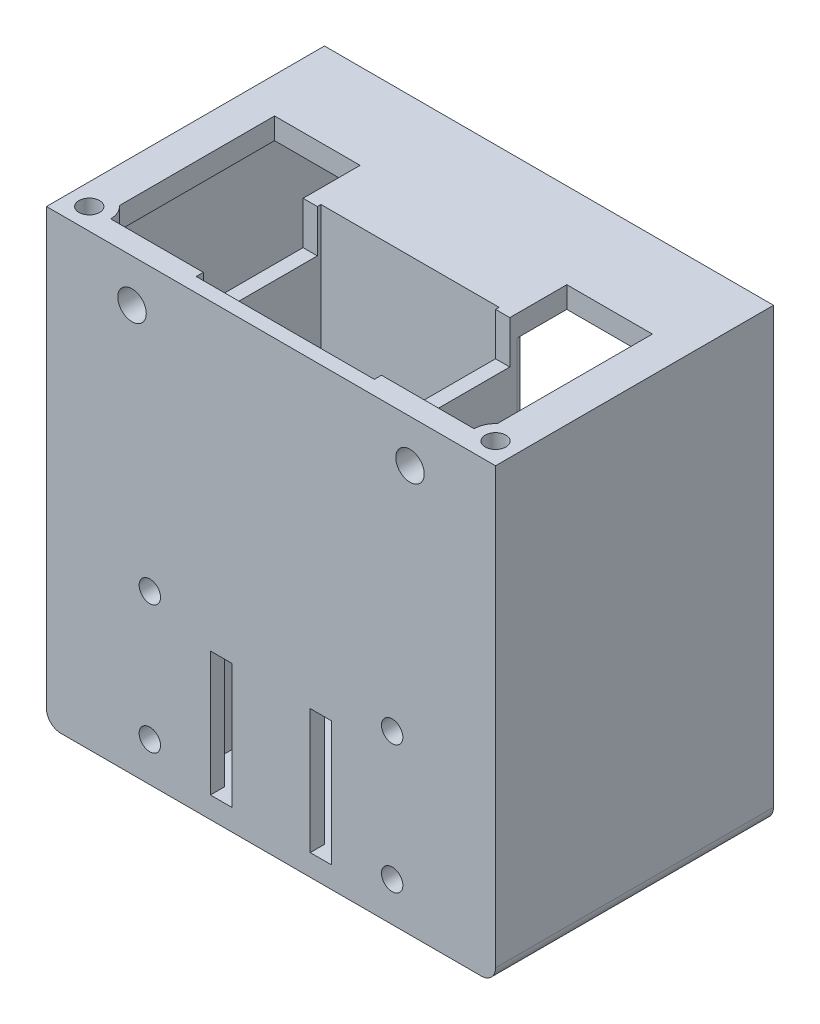
SolidWorks part; units mm, degrees
ref_plane "Alzado" through (0, 0, 0) normal (0, 0, 1) x (1, 0, 0)
ref_plane "Planta" through (0, 0, 0) normal (0, 1, 0) x (1, 0, 0)
ref_plane "Vista lateral" through (0, 0, 0) normal (1, 0, 0) x (0, 0, -1)
sketch "Croquis1" plane through (0, 0, 0) normal (0, 0, 1) x (1, 0, 0)
  line L1 (0, 0) -> (63, 0)
  line L2 (0, 0) -> (0, 63)
  line L3 (0, 63) -> (63, 63)
  line L4 (63, 0) -> (63, 63)
  line L5 (23, 20.5) -> (26, 20.5)
  line L6 (23, 20.5) -> (23, 8.5)
  line L7 (23, 8.5) -> (26, 8.5)
  line L8 (26, 20.5) -> (26, 8.5)
  line L9 (37, 20.5) -> (40, 20.5)
  line L10 (37, 20.5) -> (37, 8.5)
  line L11 (37, 8.5) -> (40, 8.5)
  line L12 (40, 20.5) -> (40, 8.5)
  circle A0 centre (12, 57) radius 2
  circle A1 centre (51, 57) radius 2
  circle A2 centre (14.5, 5.5) radius 1.5
  circle A3 centre (14.5, 23.5) radius 1.5
  circle A4 centre (48.5, 5.5) radius 1.5
  circle A5 centre (48.5, 23.5) radius 1.5
  point P21 (24.5, 8.5)
  dimension "D2" = 4
  dimension "D3" = 4
  dimension "D8" = 3
  dimension "D9" = 3
  dimension "D10" = 3
  dimension "D11" = 3
  dimension "D1" = 63
  dimension "D4" = 12
  dimension "D5" = 12
  dimension "D6" = 6
  dimension "D7" = 6
  dimension "D12" = 14.5
  dimension "D13" = 14.5
  dimension "D14" = 14.5
  dimension "D15" = 14.5
  dimension "D16" = 18
  dimension "D17" = 18
  dimension "D18" = 5.5
  dimension "D19" = 5.5
  dimension "D20" = 12
  dimension "D21" = 3
  dimension "D22" = 8.5
  dimension "D23" = 8.5
  dimension "D24" = 12
  dimension "D25" = 3
  dimension "D26" = 8.5
  dimension "D27" = 8.5
extrude "Saliente-Extruir1" add sketch "Croquis1" along normal blind 3
sketch "Croquis2" plane through (0, 0, 0) normal (0, 0, -1) x (-1, 0, 0)
  line L1 (0, 0) -> (-63, 0)
  line L2 (0, 0) -> (0, 63)
  line L3 (0, 63) -> (-63, 63)
  line L4 (-63, 0) -> (-63, 63)
  line L5 (-3, 3) -> (-60, 3)
  line L6 (-3, 3) -> (-3, 60)
  line L7 (-3, 60) -> (-60, 60)
  line L8 (-60, 3) -> (-60, 60)
  dimension "D1" = 57
  dimension "D2" = 57
  dimension "D3" = 3
  dimension "D4" = 3
extrude "Saliente-Extruir2" add sketch "Croquis2" along normal blind 36
sketch "Croquis4" plane through (0, 63, 0) normal (0, 1, 0) x (1, 0, 0)
  line L0 (63, -3) -> (0, -3) construction
  line L1 (19, 16) -> (44, 16)
  line L2 (19, 16) -> (19, -1)
  line L3 (19, -1) -> (44, -1)
  line L4 (44, 16) -> (44, -1)
  line L5 (0, -3) -> (0, 36) construction
  dimension "D1" = 25
  dimension "D2" = 17
  dimension "D3" = 2
  dimension "D4" = 19
extrude "Cortar-Extruir2" cut sketch "Croquis4" against normal blind 60
sketch "Croquis12" plane through (0, 63, 0) normal (0, 1, 0) x (1, 0, 0)
  line L0 (19, -1) -> (17, -1)
  line L2 (19, -1) -> (19, 16)
  line L3 (19, 16) -> (44, 16)
  line L4 (44, -1) -> (44, 16)
  line L6 (17, -1) -> (17, 18)
  line L7 (17, 18) -> (46, 18)
  line L8 (46, -1) -> (46, 18)
  line L9 (44, -1) -> (46, -1)
  dimension "D1" = 2
  dimension "D2" = 2
  dimension "D3" = 2
extrude "Saliente-Extruir8" add sketch "Croquis12" against normal blind 60
sketch "Croquis8" plane through (0, 0, 0) normal (-1, 0, 0) x (0, 0, 1)
  line L0 (3, 63) -> (3, 0) construction
  line L1 (-3, 20.5) -> (0, 20.5)
  line L2 (-3, 20.5) -> (-3, 8.5)
  line L3 (-3, 8.5) -> (0, 8.5)
  line L4 (0, 20.5) -> (0, 8.5)
  line L5 (3, 0) -> (-36, 0) construction
  dimension "D1" = 12
  dimension "D2" = 3
  dimension "D3" = 3
  dimension "D4" = 8.5
extrude "Cortar-Extruir4" cut sketch "Croquis8" against normal blind 63
sketch "Croquis10" plane through (0, 0, -36) normal (0, 0, -1) x (-1, 0, 0)
  circle A0 centre (-3, 3) radius 3
  circle A1 centre (-60, 3) radius 3
  dimension "D1" = 6
  dimension "D2" = 6
extrude "Saliente-Extruir6" add sketch "Croquis10" against normal blind 20
sketch "Croquis11" plane through (0, 0, -36) normal (0, 0, -1) x (-1, 0, 0)
  circle A3 centre (-60, 3) radius 1.45
  circle A5 centre (-3, 3) radius 1.45
  dimension "D4" = 2.9
  dimension "D5" = 2.9
extrude "Cortar-Extruir6" cut sketch "Croquis11" against normal blind 9
fillet "Redondeo1" radius 2 2 edges at (63, 0, -16.5) (0, 0, -16.5)
sketch "Croquis13" plane through (0, 0, -18) normal (0, 0, -1) x (-1, 0, 0)
  line L0 (-46, 3) -> (-17, 3) construction
  line L1 (-44, 3) -> (-19, 3)
  line L2 (-44, 3) -> (-44, 28)
  line L3 (-44, 28) -> (-19, 28)
  line L4 (-19, 3) -> (-19, 28)
  line L5 (-46, 3) -> (-46, 60) construction
  line L6 (-17, 3) -> (-17, 60) construction
  dimension "D1" = 2
  dimension "D2" = 2
  dimension "D3" = 25
extrude "Cortar-Extruir7" cut sketch "Croquis13" against normal blind 3
sketch "Croquis14" plane through (0, 63, 0) normal (0, 1, 0) x (1, 0, 0)
  line L0 (44, 18) -> (44, -1) construction
  line L1 (46, 20) -> (58, 20)
  line L2 (46, 20) -> (46, 0)
  line L3 (46, 0) -> (58, 0)
  line L4 (58, 20) -> (58, 0)
  line L5 (17, 0) -> (5, 0)
  line L6 (17, 0) -> (17, 20)
  line L7 (17, 20) -> (5, 20)
  line L8 (5, 0) -> (5, 20)
  line L9 (19, -1) -> (19, 18) construction
  line L10 (63, -3) -> (0, -3) construction
  dimension "D1" = 2
  dimension "D2" = 2
  dimension "D3" = 3
  dimension "D4" = 3
  dimension "D5" = 12
  dimension "D6" = 20
  dimension "D7" = 12
  dimension "D8" = 20
extrude "Cortar-Extruir8" cut sketch "Croquis14" against normal blind 5
sketch "Croquis15" plane through (0, 63, 0) normal (0, 1, 0) x (1, 0, 0)
  line L0 (63, -3) -> (0, -3) construction
  line L1 (0, -3) -> (0, 36) construction
  line L3 (63, -3) -> (63, 36) construction
  line L4 (0, 36) -> (63, 36) construction
  circle A0 centre (3, 0) radius 3
  circle A1 centre (60, 0) radius 3
  circle A2 centre (31.5, 31) radius 3
  dimension "D1" = 6
  dimension "D2" = 6
  dimension "D3" = 6
  dimension "D4" = 31.5
  dimension "D5" = 5
extrude "Saliente-Extruir9" add sketch "Croquis15" against normal blind 20
sketch "Croquis16" plane through (0, 60, 0) normal (0, -1, 0) x (1, 0, 0)
  line L0 (17, -18) -> (46, -18) construction
  line L1 (24, -18) -> (39, -18)
  line L2 (24, -18) -> (24, -36)
  line L3 (24, -36) -> (39, -36)
  line L4 (39, -18) -> (39, -36)
  line L5 (3, -36) -> (60, -36) construction
extrude "Saliente-Extruir10" add sketch "Croquis16" along normal blind 8
sketch "Croquis17" plane through (0, 63, 0) normal (0, 1, 0) x (1, 0, 0)
  line L0 (0, 36) -> (63, 36) construction
  line L1 (0, -3) -> (0, 36) construction
  circle A0 centre (3, 0) radius 1.45
  circle A1 centre (60, 0) radius 1.45
  circle A2 centre (31.5, 31) radius 1.45
  dimension "D1" = 2.9
  dimension "D2" = 2.9
  dimension "D3" = 2.9
  dimension "D4" = 5
  dimension "D5" = 31.5
extrude "Cortar-Extruir9" cut sketch "Croquis17" against normal blind 20
sketch "Croquis18" plane through (63, 0, 0) normal (1, 0, 0) x (0, 0, -1)
  line L1 (0, 8.5) -> (3, 8.5)
  line L2 (0, 8.5) -> (0, 20.5)
  line L3 (0, 20.5) -> (3, 20.5)
  line L4 (3, 8.5) -> (3, 20.5)
extrude "Saliente-Extruir11" add sketch "Croquis18" against normal blind 3
sketch "Croquis19" plane through (0, 0, 0) normal (-1, 0, 0) x (0, 0, 1)
  line L1 (-3, 8.5) -> (0, 8.5)
  line L2 (-3, 8.5) -> (-3, 20.5)
  line L3 (-3, 20.5) -> (0, 20.5)
  line L4 (0, 8.5) -> (0, 20.5)
extrude "Saliente-Extruir12" add sketch "Croquis19" against normal blind 3
fillet "Redondeo3" radius 1 10 edges at (31.5, 28, -18) (44, 15.5, -18) (19, 15.5, -18) (46, 31.5, -18) (17, 31.5, -18) (39, 52, -27) (24, 52, -27) (39, 56, -36) (24, 56, -36) (31.5, 52, -36)
sketch "Croquis20" plane through (0, 0, 0) normal (0, -1, 0) x (1, 0, 0)
  line L0 (2, 3) -> (61, 3) construction
  line L1 (0, -36) -> (0, 3) construction
  circle A0 centre (10, -4) radius 3.125
  circle A1 centre (10, -14) radius 2.625
  dimension "D1" = 6.25
  dimension "D3" = 5.25
  dimension "D2" = 7
  dimension "D4" = 10
  dimension "D5" = 10
  dimension "D6" = 10
extrude "Cortar-Extruir10" cut sketch "Croquis20" against normal blind 3
sketch "Croquis21" plane through (0, 0, -36) normal (0, 0, -1) x (-1, 0, 0)
  line L0 (-3, 60) -> (-25, 60) construction
  line L1 (-22.4776, 60) -> (-41.3134, 60)
  line L2 (-22.4776, 60) -> (-22.4776, 40.1042)
  line L3 (-22.4776, 40.1042) -> (-41.3134, 40.1042)
  line L4 (-41.3134, 60) -> (-41.3134, 40.1042)
extrude "Cortar-Extruir11" cut sketch "Croquis21" against normal up to surface (18 mm away) up to face at (31.5, 50.7586, -18)
sketch "Croquis22" plane through (0, 63, 0) normal (0, 1, 0) x (1, 0, 0)
  circle A0 centre (31.5, 31) radius 1.45
extrude "Saliente-Extruir13" add sketch "Croquis22" against normal up to surface (3 mm away)
sketch "Croquis23" plane through (0, 63, 0) normal (0, 1, 0) x (1, 0, 0)
  line L0 (46, 0) -> (46, 17) construction
  line L1 (17, 0) -> (46, 0)
  line L2 (17, 0) -> (17, 16)
  line L3 (17, 16) -> (46, 16)
  line L4 (46, 0) -> (46, 16)
  line L5 (44, 16) -> (19, 16) construction
extrude "Cortar-Extruir12" cut sketch "Croquis23" against normal blind 6
sketch "Croquis24" plane through (0, 0, 1) normal (0, 0, -1) x (-1, 0, 0)
  line L0 (-57, 3) -> (-6, 3) construction
  line L1 (-40, 8.5) -> (-37, 8.5)
  line L2 (-40, 8.5) -> (-40, 3)
  line L3 (-40, 3) -> (-37, 3)
  line L4 (-37, 8.5) -> (-37, 3)
  line L5 (-37, 20.5) -> (-37, 8.5) construction
  line L6 (-19, 3) -> (-44, 3) construction
  line L7 (-26, 8.5) -> (-23, 8.5)
  line L8 (-26, 8.5) -> (-26, 3)
  line L9 (-26, 3) -> (-23, 3)
  line L10 (-23, 8.5) -> (-23, 3)
  line L11 (-23, 20.5) -> (-23, 8.5) construction
extrude "Cortar-Extruir13" cut sketch "Croquis24" against normal blind 6
sketch "Croquis25" plane through (46, 0, 0) normal (1, 0, 0) x (0, 0, -1)
  line L0 (7.125, 3) -> (0.875, 3) construction
  line L1 (0, 8.5) -> (3, 8.5)
  line L2 (0, 8.5) -> (0, 3)
  line L3 (0, 3) -> (3, 3)
  line L4 (3, 8.5) -> (3, 3)
  line L5 (3, 8.5) -> (3, 20.5) construction
extrude "Cortar-Extruir14" cut sketch "Croquis25" against normal blind 30
sketch "Croquis26" plane through (0, 63, 0) normal (0, 1, 0) x (1, 0, 0)
  line L0 (46, 16) -> (17, 16) construction
  line L1 (19, 16) -> (44, 16)
  line L2 (19, 16) -> (19, 16.5)
  line L3 (19, 16.5) -> (44, 16.5)
  line L4 (44, 16) -> (44, 16.5)
  line L5 (19, 17) -> (19, 3) construction
  line L6 (44, 3) -> (44, 17) construction
  dimension "D1" = 0.5
extrude "Cortar-Extruir15" cut sketch "Croquis26" against normal blind 60
sketch "Croquis28" plane through (0, 63, 0) normal (0, 1, 0) x (1, 0, 0)
  line L0 (17, 16) -> (17, 20) construction
  line L1 (5, 20) -> (17, 20)
  line L2 (5, 20) -> (5, 24)
  line L3 (5, 24) -> (17, 24)
  line L4 (17, 20) -> (17, 24)
  line L5 (46, 20) -> (58, 20)
  line L6 (46, 20) -> (46, 24)
  line L7 (46, 24) -> (58, 24)
  line L8 (58, 20) -> (58, 24)
  line L9 (58, 2.2361) -> (58, 20) construction
  dimension "D1" = 4
  dimension "D2" = 4
extrude "Cortar-Extruir16" cut sketch "Croquis28" against normal blind 6
sketch "Croquis29" plane through (0, 0, 0) normal (-1, 0, 0) x (0, 0, 1)
  line L0 (-36, 2) -> (3, 2) construction
  line L1 (-36, 10) -> (-15, 10)
  line L2 (-36, 10) -> (-36, 12)
  line L3 (-34, 12) -> (-17, 12)
  line L4 (-15, 10) -> (-15, 12)
  line L6 (-36, 12) -> (-36, 47)
  line L7 (-36, 47) -> (-34, 47)
  line L8 (-34, 12) -> (-34, 47)
  line L10 (-15, 12) -> (-15, 47)
  line L11 (-15, 47) -> (-17, 47)
  line L12 (-17, 12) -> (-17, 47)
  line L13 (-36, 2) -> (-36, 63) construction
  dimension "D1" = 21
  dimension "D2" = 2
  dimension "D3" = 2
  dimension "D4" = 2
  dimension "D5" = 37
  dimension "D6" = 37
  dimension "D7" = 8
  dimension "D8" = 2
extrude "Saliente-Extruir14" add sketch "Croquis29" along normal blind 4.6
sketch "Croquis30" plane through (-4.6, 0, 0) normal (-1, 0, 0) x (0, 0, 1)
  line L0 (-15, 10) -> (-15, 47) construction
  line L1 (-36, 10) -> (-15, 10)
  line L2 (-36, 10) -> (-36, 14)
  line L3 (-32, 14) -> (-19, 14)
  line L4 (-15, 10) -> (-15, 14)
  line L6 (-36, 47) -> (-32, 47)
  line L7 (-36, 47) -> (-36, 14)
  line L9 (-32, 47) -> (-32, 14)
  line L10 (-15, 47) -> (-19, 47)
  line L11 (-15, 47) -> (-15, 14)
  line L13 (-19, 47) -> (-19, 14)
  dimension "D1" = 4
  dimension "D2" = 4
  dimension "D3" = 4
  dimension "D4" = 4
extrude "Saliente-Extruir15" add sketch "Croquis30" along normal blind 1.5
fillet "Redondeo4" radius 2 5 edges at (-3.05, 10, -36) (-3.05, 10, -15) (-6.1, 10, -25.5) (-6.1, 28.5, -15) (-6.1, 28.5, -36)
sketch "Croquis31" plane through (-6.1, 0, 0) normal (-1, 0, 0) x (0, 0, 1)
  line L0 (-32, 14) -> (-32, 47) construction
  line L1 (-34, 47) -> (-32, 47)
  line L2 (-34, 47) -> (-34, 44)
  line L3 (-34, 44) -> (-32, 44)
  line L4 (-32, 47) -> (-32, 44)
  dimension "D1" = 3
extrude "Cortar-Extruir17" cut sketch "Croquis31" against normal blind 2
